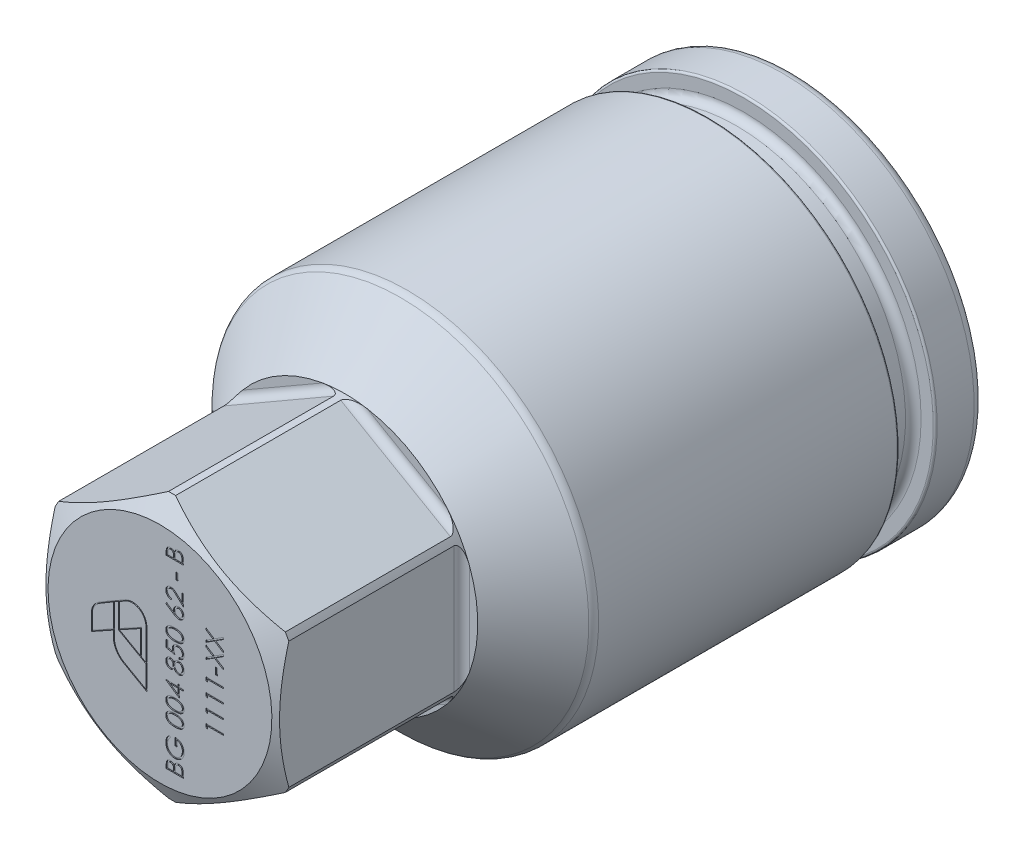
SolidWorks part; units mm, degrees
material "4340 H/T-Y"
ref_plane "Front Plane" through (0, 0, 0) normal (0, 0, 1) x (1, 0, 0)
ref_plane "Top Plane" through (0, 0, 0) normal (0, 1, 0) x (1, 0, 0)
ref_plane "Right Plane" through (0, 0, 0) normal (1, 0, 0) x (0, 0, -1)
sketch "Sketch1" plane through (0, 0, 0) normal (1, 0, 0) x (0, 0, -1)
  line L0 (0, 13) -> (0, 18.65)
  line L1 (0, 0) -> (-34, 0) construction
  line L2 (-1, 19.65) -> (-4.8, 19.65)
  line L3 (-40.2929, 19.3571) -> (-46, 13.65)
  line L4 (-46, 13.65) -> (-63.7587, 13.65)
  line L5 (-63.7587, 13.65) -> (-65, 11.5)
  line L6 (-65, 11.5) -> (-65, 0)
  line L7 (-65, 0) -> (-39, 0)
  line L8 (-34, 8.3214) -> (-34, 10.5)
  line L9 (-32, 12.5) -> (-31.5981, 12.5)
  line L10 (-31.5981, 12.5) -> (-29, 11)
  line L11 (-29, 11) -> (-2, 11)
  line L12 (-2, 11) -> (0, 13)
  line L13 (-34, 8.3214) -> (-39, 0)
  line L14 (-8.7, 19.45) -> (-8.7, 18.2)
  line L15 (-7.9, 17.4) -> (-5.8, 17.4)
  line L16 (-5, 18.2) -> (-5, 19.45)
  line L17 (-8.9, 19.65) -> (-39.5858, 19.65)
  arc A0 (0, 18.65) -> (-1, 19.65) centre (-1, 18.65) ccw
  arc A1 (-40.2929, 19.3571) -> (-39.5858, 19.65) centre (-39.5858, 18.65) cw
  arc A2 (-34, 10.5) -> (-32, 12.5) centre (-32, 10.5) cw
  arc A3 (-5.8, 17.4) -> (-5, 18.2) centre (-5.8, 18.2) ccw
  arc A4 (-8.7, 18.2) -> (-7.9, 17.4) centre (-7.9, 18.2) ccw
  arc A5 (-5, 19.45) -> (-4.8, 19.65) centre (-4.8, 19.45) cw
  arc A6 (-8.7, 19.45) -> (-8.9, 19.65) centre (-8.9, 19.45) ccw
  point P18 (-40, 19.65)
  point P35 (-8.7, 19.65)
  dimension "D3" = 1
  dimension "D16" = 1
  dimension "D19" = 2
  dimension "D24" = 0.8
  dimension "D25" = 0.2
  dimension "D1" = 65
  dimension "D2" = 40
  dimension "D4" = 34
  dimension "D5" = 22
  dimension "D6" = 25
  dimension "D7" = 26
  dimension "D8" = 45
  dimension "D9" = 30
  dimension "D10" = 29
  dimension "D11" = 39.3
  dimension "D12" = 27.3
  dimension "D13" = 60
  dimension "D14" = 23
  dimension "D15" = 45
  dimension "D17" = 39
  dimension "D18" = 59
  dimension "D20" = 5
  dimension "D21" = 3.7
  dimension "D22" = 34.8
  dimension "D23" = 46
revolve "Revolve1" add sketch "Sketch1" angle 360 about L1
cosmetic thread "Cosmetic Thread1" parameters "D1"=29, "D2"=24
sketch "Sketch2" plane through (0, 0, 65) normal (0, 0, 1) x (1, 0, 0)
  line L1 (0, -13.8564) -> (12, -6.9282)
  line L2 (12, -6.9282) -> (12, 6.9282)
  line L3 (12, 6.9282) -> (0, 13.8564)
  line L4 (0, 13.8564) -> (-12, 6.9282)
  line L5 (-12, 6.9282) -> (-12, -6.9282)
  line L6 (-12, -6.9282) -> (0, -13.8564)
  circle A0 centre (0, 0) radius 12 construction
  dimension "D1" = 24
extrude "Cut-Extrude1" cut sketch "Sketch2" against normal blind 19 flip side to cut
sketch "Sketch3" plane through (0, 0, 65) normal (0, 0, 1) x (1, 0, 0)
  line L0 (2.4417, -11.0588) -> (2.4417, 11.2378) construction
  circle A0 centre (0, 0) radius 11.5 construction
  text T0 "BG 004 850 62 - B\r\n1111-XX" font "Century Gothic" height 1.8
  line B0 (-1.3478, 1.726) -> (-1.3478, -1.5424)
  line B1 (-2.014, 1.2419) -> (-2.014, -1.1635)
  line B2 (-1.4478, -1.4855) -> (-1.914, -1.2204)
  line B3 (-4.792, -0.2844) -> (-4.792, -0.8544)
  line B4 (-7.0559, -1.5424) -> (-4.792, -0.2844)
  line B5 (-2.014, 1.2419) -> (-4.1613, 0.0575)
  line B6 (-4.1613, 2.6869) -> (-3.6449, 2.9857)
  line B7 (-7.0559, 0.0616) -> (-7.0559, -1.5424)
  line B8 (-4.792, 2.3429) -> (-4.1613, 2.6869)
  line B9 (-4.792, 2.3429) -> (-6.2485, 1.4791)
  line B10 (-1.3478, -1.5424) -> (-1.3478, -4.0398)
  line B11 (-3.8169, -2.6358) -> (-1.3478, -4.0398)
  line B12 (-4.2616, 2.5412) -> (-4.692, 2.286)
  line B13 (-6.9559, 0.0616) -> (-6.9559, -1.3724)
  line B14 (-6.9559, -1.3724) -> (-4.792, -0.17)
  line B15 (-4.692, -0.8544) -> (-4.692, 2.286)
  line B16 (-3.7652, -2.5501) -> (-1.4478, -3.8679)
  line B17 (-1.4478, -1.6006) -> (-1.4478, -3.8679)
  line B18 (-4.2616, -0.0005) -> (-4.2616, 2.5412)
  line B19 (-1.4478, -1.6006) -> (-4.2616, -0.0005)
  line B20 (-4.1613, 2.5713) -> (-3.5929, 2.9002)
  line B21 (-1.4478, 1.726) -> (-1.4478, -1.4855)
  line B22 (-4.792, -0.17) -> (-4.792, 2.2267)
  line B23 (-4.792, 2.2267) -> (-6.1975, 1.3931)
  line B24 (-1.914, 1.4113) -> (-1.914, -1.2204)
  line B25 (-1.914, 1.4113) -> (-4.1613, 0.1717)
  line B26 (-4.1613, 0.1717) -> (-4.1613, 2.5713)
  line B27 (-2.014, -1.1635) -> (-4.1613, 0.0575)
  arc B28 (-6.2485, 1.4791) -> (-7.0559, 0.0616) centre (-5.4079, 0.0616) ccw
  arc B29 (-1.3478, 1.726) -> (-3.6449, 2.9857) centre (-2.8417, 1.726) ccw
  arc B30 (-4.792, -0.8544) -> (-3.8169, -2.6358) centre (-2.6773, -0.8544) ccw
  arc B31 (-6.1975, 1.3931) -> (-6.9559, 0.0616) centre (-5.4079, 0.0616) ccw
  arc B32 (-4.692, -0.8544) -> (-3.7652, -2.5501) centre (-2.6773, -0.8544) ccw
  arc B33 (-1.4478, 1.726) -> (-3.5929, 2.9002) centre (-2.8417, 1.726) ccw
sketch_block_instance "SKETCH LOGO-1"
sketch_block "SKETCH LOGO" parameters "D1"=29.059, "D2"=11.4163, "D3"=29.624, "D4"=6.8884
extrude "Cut-Extrude2" cut sketch "Sketch3" against normal blind 0.1
fillet "Fillet1" radius 0.8 6 edges at (-12, 0, 46) (-6, -10.3923, 46) (6, -10.3923, 46) (12, 0, 46) (-6, 10.3923, 46) (6, 10.3923, 46)
